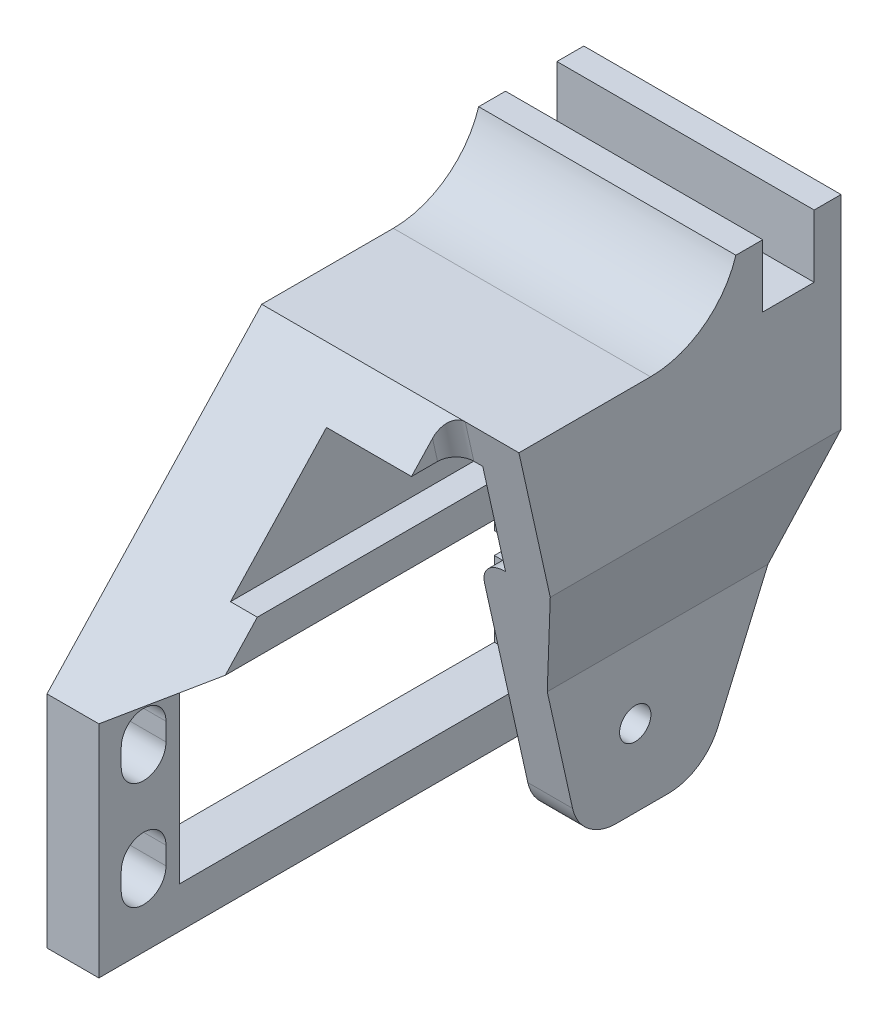
SolidWorks part; units mm, degrees
ref_plane "Front Plane" through (0, 0, 0) normal (0, 0, 1) x (1, 0, 0)
ref_plane "Top Plane" through (0, 0, 0) normal (0, 1, 0) x (1, 0, 0)
ref_plane "Right Plane" through (0, 0, 0) normal (1, 0, 0) x (0, 0, -1)
sketch "Sketch1" plane through (0, 0, 0) normal (0, 0, 1) x (1, 0, 0)
  line L0 (391.7164, -195.1284) -> (404.2164, -195.1284)
  line L1 (404.2164, -195.1284) -> (404.2164, -206.5784)
  line L7 (386.2664, -241.1507) -> (386.2664, -216.5477)
  line L8 (386.2664, -216.5477) -> (394.7164, -210.4621)
  line L9 (394.7164, -210.4621) -> (394.7164, -206.6284)
  line L10 (394.7164, -206.6284) -> (391.7164, -206.6284)
  line L11 (391.7164, -206.6284) -> (391.7164, -195.1284)
  line L15 (386.2664, -241.1507) -> (380.4664, -241.1507)
  line L16 (400.9664, -211.8763) -> (400.9664, -206.3784) construction
  line L17 (400.9664, -206.3784) -> (403.9664, -206.3784) construction
  line L18 (403.9664, -206.3784) -> (403.9664, -195.3784) construction
  line L19 (403.9664, -195.3784) -> (391.9664, -195.3784) construction
  line L20 (391.9664, -195.3784) -> (391.9664, -206.3784) construction
  line L21 (391.9664, -206.3784) -> (394.9664, -206.3784) construction
  line L22 (394.9664, -206.3784) -> (394.9664, -211.8763) construction
  line L23 (394.9664, -211.8763) -> (400.9664, -211.8763) construction
  line L24 (380.4664, -241.1507) -> (380.4664, -190.836)
  line L25 (380.4664, -190.836) -> (409.2164, -190.836)
  line L27 (406.2164, -235.1694) -> (401.2164, -235.1694)
  line L30 (406.2164, -235.1694) -> (406.2164, -218.5477)
  line L31 (406.2164, -218.5477) -> (409.2164, -206.5784)
  line L32 (409.2164, -206.5784) -> (409.2164, -190.836)
  line L36 (401.2164, -209.5784) -> (401.2164, -235.1694)
  arc A0 (404.2164, -206.5784) -> (401.2164, -209.5784) centre (404.2164, -209.5784) ccw
  point P17 (0, 0)
  point P23 (0, 0)
  point P25 (0, 0)
  point P28 (393.2164, -206.6284)
  dimension "D1" = 0.25
  dimension "D2" = 0.25
  dimension "D3" = 0.25
  dimension "D4" = 0.25
  dimension "D5" = 5.8
  dimension "D7" = 5
  dimension "D8" = 0.25
  dimension "D9" = 11.5
extrude "Boss-Extrude1" add sketch "Sketch1" along normal blind 60
sketch "Sketch4" plane through (380.4664, 0, 0) normal (-1, 0, 0) x (0, 0, 1)
  line L0 (57.5, -232.0477) -> (57.5, -234.0477)
  line L2 (60, -190.836) -> (60, -241.1507) construction
  line L3 (10, -216.5477) -> (51, -216.5477)
  line L4 (10, -216.5477) -> (10, -236.5477)
  line L5 (10, -236.5477) -> (51, -236.5477)
  line L6 (51, -216.5477) -> (51, -236.5477)
  line L7 (8.5, -222.0477) -> (8.5, -220.0477)
  line L8 (3.5, -220.0477) -> (3.5, -222.0477)
  line L9 (3.5, -232.0477) -> (3.5, -234.0477)
  line L10 (8.5, -234.0477) -> (8.5, -232.0477)
  line L11 (52.5, -234.0477) -> (52.5, -232.0477)
  line L12 (57.5, -220.0477) -> (57.5, -222.0477)
  line L13 (52.5, -222.0477) -> (52.5, -220.0477)
  line L14 (60, -216.5477) -> (0, -216.5477) construction
  line L15 (60, -216.5477) -> (0, -216.5477) construction
  arc A0 (8.5, -220.0477) -> (3.5, -220.0477) centre (6, -220.0477) ccw
  arc A1 (3.5, -222.0477) -> (8.5, -222.0477) centre (6, -222.0477) ccw
  arc A2 (3.5, -234.0477) -> (8.5, -234.0477) centre (6, -234.0477) ccw
  arc A3 (3.5, -232.0477) -> (8.5, -232.0477) centre (6, -232.0477) cw
  arc A4 (57.5, -234.0477) -> (52.5, -234.0477) centre (55, -234.0477) cw
  arc A5 (52.5, -232.0477) -> (57.5, -232.0477) centre (55, -232.0477) cw
  arc A6 (57.5, -222.0477) -> (52.5, -222.0477) centre (55, -222.0477) cw
  arc A7 (52.5, -220.0477) -> (57.5, -220.0477) centre (55, -220.0477) cw
  dimension "D7" = 5
  dimension "D1" = 41
  dimension "D2" = 9
  dimension "D3" = 5
  dimension "D4" = 1.5
  dimension "D5" = 2
  dimension "D6" = 3.5
  dimension "D8" = 10
  dimension "D9" = 2
  dimension "D10" = 5
  dimension "D11" = 2
  dimension "D12" = 1.5
  dimension "D13" = 2
  dimension "D14" = 5
  dimension "D15" = 3.5
  dimension "D16" = 10
  dimension "D17" = 20
extrude "Cut-Extrude1" cut sketch "Sketch4" against normal up to surface (5.8 mm away) up to face at (386.2664, -228.8492, 30)
sketch "Sketch5" plane through (0, -241.1507, 0) normal (0, -1, 0) x (1, 0, 0)
  line L0 (380.4664, 10) -> (380.4664, 51) construction
  line L1 (380.4664, 10) -> (380.4664, 51) construction
  line L2 (380.4664, 51) -> (382.6664, 51)
  line L4 (380.4664, 60) -> (380.4664, 0) construction
  line L5 (380.4664, 57.2) -> (380.4664, 51)
  line L6 (380.4664, 10) -> (382.6664, 10)
  line L8 (380.4664, 3.8) -> (380.4664, 10)
  line L9 (380.4664, 3.8) -> (381.4664, 3.8)
  line L10 (381.4664, 3.8) -> (382.6664, 8.5)
  line L11 (382.6664, 8.5) -> (382.6664, 10)
  line L12 (382.6664, 51) -> (382.6664, 52.5)
  line L13 (382.6664, 52.5) -> (381.4664, 57.2)
  line L14 (381.4664, 57.2) -> (380.4664, 57.2)
  dimension "D1" = 6.2
  dimension "D2" = 6.2
  dimension "D3" = 2.2
  dimension "D4" = 2.2
  dimension "D5" = 1.5
  dimension "D6" = 1
  dimension "D7" = 1
  dimension "D8" = 1.5
extrude "Cut-Extrude2" cut sketch "Sketch5" against normal blind 1.4 and the other way blind 1 from offset 14 offset against normal yes
sketch "Sketch2" plane through (406.2164, 0, 0) normal (1, 0, 0) x (0, 0, -1)
  line L0 (-10, -236.5477) -> (-10, -216.5477) construction
  line L1 (-10, -216.5477) -> (-51, -216.5477) construction
  circle A0 centre (-20, -226.5477) radius 1.75
  dimension "D1" = 3.5
  dimension "D2" = 10
  dimension "D3" = 10
extrude "Cut-Extrude3" cut sketch "Sketch2" against normal up to surface (5 mm away) up to face at (401.2164, -222.3739, 30)
sketch "Sketch6" plane through (409.2164, 0, 0) normal (1, 0, 0) x (0, 0, -1)
  line L0 (-60, -190.836) -> (0, -190.836) construction
  line L1 (0, -190.836) -> (-3, -190.836)
  line L2 (0, -190.836) -> (0, -183.836)
  line L3 (0, -183.836) -> (-3, -183.836)
  line L4 (-3, -190.836) -> (-3, -183.836)
  line L5 (-8.75, -190.836) -> (-11.75, -190.836)
  line L6 (-8.75, -190.836) -> (-8.75, -183.836)
  line L7 (-8.75, -183.836) -> (-11.75, -183.836)
  line L8 (-11.75, -190.836) -> (-11.75, -183.836)
  dimension "D1" = 7
  dimension "D2" = 7
  dimension "D3" = 5.75
  dimension "D4" = 3
  dimension "D5" = 3
extrude "Boss-Extrude2" add sketch "Sketch6" against normal up to surface (28.75 mm away) up to face at (380.4664, -215.9933, 30)
fillet "Fillet1" radius 10 1 edges at (394.8414, -190.836, 11.75)
sketch "Sketch7" plane through (380.4664, 0, 0) normal (-1, 0, 0) x (0, 0, 1)
  line L0 (60, -190.836) -> (36, -190.836)
  line L1 (60, -190.836) -> (21.2894, -190.836) construction
  line L2 (36, -190.836) -> (60, -216.5477)
  line L3 (60, -190.836) -> (60, -241.1507) construction
  line L4 (51, -216.5477) -> (10, -216.5477) construction
  line L5 (51, -216.5477) -> (9, -216.5477) construction
  line L6 (60, -216.5477) -> (60, -190.836)
  dimension "D1" = 24
extrude "Cut-Extrude4" cut sketch "Sketch7" against normal up to surface (28.75 mm away) up to face at (409.2164, -191.3407, 17.5393)
sketch "Sketch8" plane through (409.2164, 0, 0) normal (1, 0, 0) x (0, 0, -1)
  line L1 (-60, -235.1694) -> (0, -235.1694) construction
  line L2 (-60, -235.1694) -> (0, -235.1694) construction
  line L3 (-36, -235.1694) -> (-60, -235.1694)
  line L5 (-60, -235.1694) -> (-60, -190.836)
  line L6 (-60, -190.836) -> (-36, -190.836)
  line L7 (-36, -190.836) -> (-26.1358, -235.1694)
  line L8 (-26.1358, -235.1694) -> (-36, -235.1694)
extrude "Cut-Extrude5" cut sketch "Sketch8" against normal up to surface (8 mm away) up to face at (401.2164, -226.5477, 18.25)
sketch "Sketch10" plane through (409.2164, 0, 0) normal (1, 0, 0) x (0, 0, -1)
  line L0 (0, -206.5784) -> (0, -242.7535)
  line L1 (0, -242.7535) -> (-15.6224, -242.7535)
  line L2 (-15.6224, -242.7535) -> (0, -206.5784)
extrude "Cut-Extrude6" cut sketch "Sketch10" against normal up to surface (8 mm away) up to face at (401.2164, -226.5477, 18.25)
fillet "Fillet2" radius 5 1 edges at (403.7164, -235.1694, 26.1358)
fillet "Fillet3" radius 6 1 edges at (403.7164, -235.1694, 12.3471)
fillet "Fillet4" radius 2 1 edges at (401.2164, -192.9822, 35.5225)
